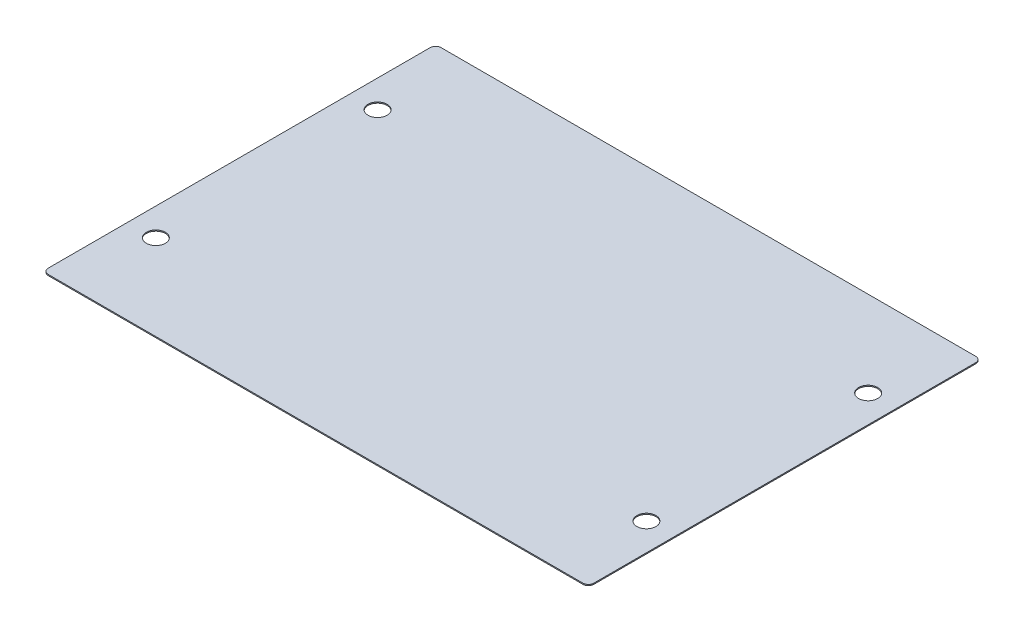
SolidWorks part; units mm, degrees
ref_plane "Front Plane" through (0, 0, 0) normal (0, 0, 1) x (1, 0, 0)
ref_plane "Top Plane" through (0, 0, 0) normal (0, 1, 0) x (1, 0, 0)
ref_plane "Right Plane" through (0, 0, 0) normal (1, 0, 0) x (0, 0, -1)
sketch "Sketch2" plane through (0, 0, 0) normal (0, 1, 0) x (1, 0, 0)
  line L4 (0.5711, -14.0687) -> (0.5711, 20.9313)
  line L5 (-48.9289, -14.5687) -> (0.0711, -14.5687)
  line L6 (-49.4289, 20.9313) -> (-49.4289, -14.0687)
  line L7 (0.0711, 21.4313) -> (-48.9289, 21.4313)
  line L8 (0.5711, -14.0687) -> (0.5711, 20.9313)
  line L9 (-48.9289, -14.5687) -> (0.0711, -14.5687)
  line L10 (-49.4289, 20.9313) -> (-49.4289, -14.0687)
  line L11 (0.0711, 21.4313) -> (-48.9289, 21.4313)
  arc A4 (0.5711, 20.9313) -> (0.0711, 21.4313) centre (0.0711, 20.9313) ccw
  arc A5 (0.0711, -14.5687) -> (0.5711, -14.0687) centre (0.0711, -14.0687) ccw
  arc A6 (-49.4289, -14.0687) -> (-48.9289, -14.5687) centre (-48.9289, -14.0687) ccw
  arc A7 (-48.9289, 21.4313) -> (-49.4289, 20.9313) centre (-48.9289, 20.9313) ccw
  arc A8 (0.5711, 20.9313) -> (0.0711, 21.4313) centre (0.0711, 20.9313) ccw
  arc A9 (0.0711, -14.5687) -> (0.5711, -14.0687) centre (0.0711, -14.0687) ccw
  arc A10 (-49.4289, -14.0687) -> (-48.9289, -14.5687) centre (-48.9289, -14.0687) ccw
  arc A11 (-48.9289, 21.4313) -> (-49.4289, 20.9313) centre (-48.9289, 20.9313) ccw
  circle A20 centre (-1.9489, 13.5913) radius 0.875 construction
  circle A21 centre (-46.9089, 13.5913) radius 0.875 construction
  circle A22 centre (-46.9089, -6.7287) radius 0.875 construction
  circle A23 centre (-1.9489, -6.7287) radius 0.875 construction
  circle A24 centre (-1.9489, 13.5913) radius 0.875
  circle A25 centre (-46.9089, 13.5913) radius 0.875
  circle A26 centre (-46.9089, -6.7287) radius 0.875
  circle A27 centre (-1.9489, -6.7287) radius 0.875
  dimension "D1" = 0
extrude "Boss-Extrude2" add sketch "Sketch2" along normal blind 0.1
